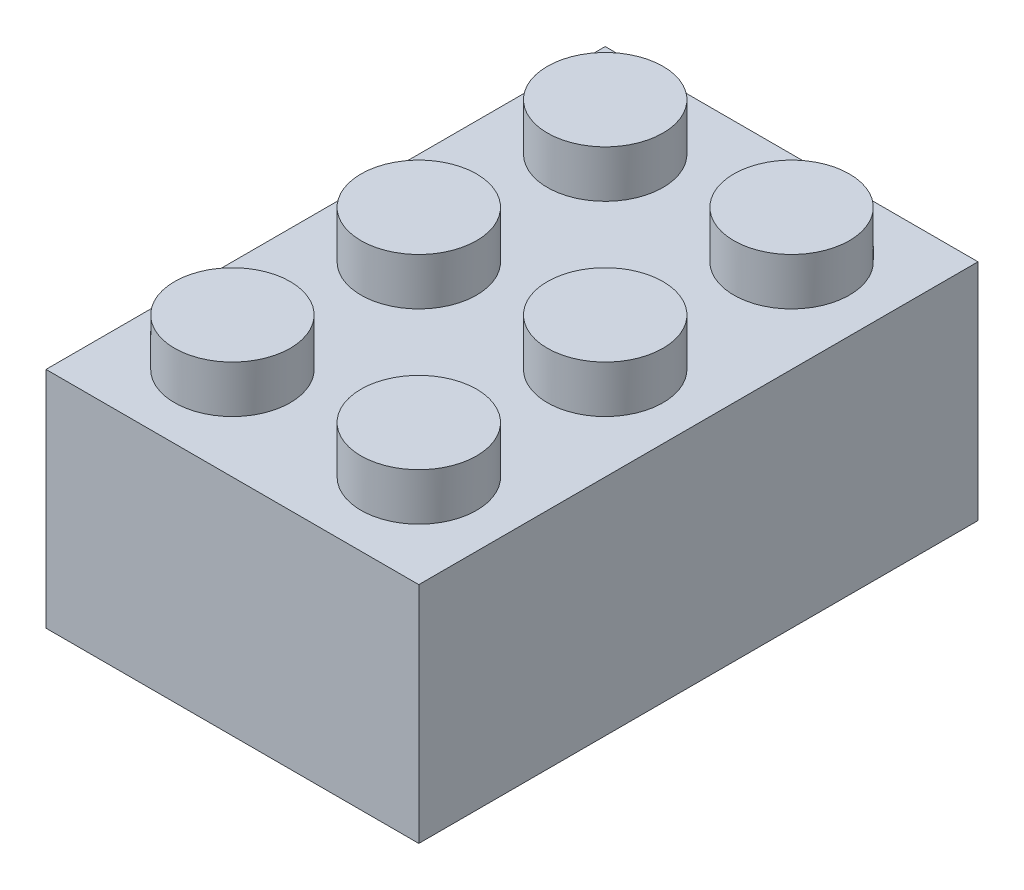
SolidWorks part; units mm, degrees
ref_plane "Front Plane" through (0, 0, 0) normal (0, 0, 1) x (1, 0, 0)
ref_plane "Top Plane" through (0, 0, 0) normal (0, 1, 0) x (1, 0, 0)
ref_plane "Right Plane" through (0, 0, 0) normal (1, 0, 0) x (0, 0, -1)
sketch "stencil" plane through (0, 0, 0) normal (0, 1, 0) x (1, 0, 0)
  line L2 (14.3, 22.2) -> (1.5, 22.2)
  line L29 (15.8, 23.7) -> (0, 23.7)
  line L37 (15.8, 23.7) -> (15.8, 0)
  line L38 (15.8, 0) -> (0, 0)
  line L39 (0, 23.7) -> (0, 0)
  line L40 (7.9, 0) -> (7.9, 23.7) construction
  line L41 (15.8, 11.85) -> (0, 11.85) construction
  line L50 (1.5, 22.2) -> (1.5, 1.5)
  line L51 (14.3, 1.5) -> (1.5, 1.5)
  line L52 (14.3, 22.2) -> (14.3, 1.5)
  circle A43 centre (3.95, 3.95) radius 2.45
  circle A44 centre (7.9, 7.9) radius 3.25
  circle A46 centre (3.95, 11.85) radius 2.45
  circle A47 centre (7.9, 15.8) radius 3.25
  circle A49 centre (3.95, 19.75) radius 2.45
  circle A50 centre (11.85, 19.75) radius 2.45
  circle A51 centre (11.85, 11.85) radius 2.45
  circle A52 centre (11.85, 3.95) radius 2.45
  circle A53 centre (7.9, 15.8) radius 2.45
  circle A54 centre (7.9, 7.9) radius 2.45
  point P1 (0, 0)
  point P6 (3.95, -15.8)
  point P9 (7.9, -15.8)
  point P10 (7.9, -11.85)
  point P13 (3.95, -7.9)
  point P15 (7.9, -7.9)
  point P17 (7.9, -3.95)
  point P18 (3.95, 0)
  point P21 (7.9, 0)
  point P25 (7.9, 3.95)
  point P27 (3.95, 7.9)
  point P28 (7.9, 7.9)
  point P29 (0, -11.85)
  point P30 (0, -7.9)
  point P31 (0, 3.95)
  point P34 (0, -3.95)
  point P35 (3.95, 0)
  point P36 (0, 15.8)
  point P37 (0, 23.7)
  point P38 (7.9, 23.7)
  point P39 (15.8, 23.7)
  point P40 (15.8, 15.8)
  point P41 (15.8, 7.9)
  point P48 (15.8, 0)
  point P49 (7.9, 0)
  point P51 (11.85, 0)
  point P52 (3.95, 3.95)
  point P53 (7.9, 3.95)
  point P55 (11.85, 3.95)
  point P56 (3.95, 7.9)
  point P57 (7.9, 7.9)
  point P58 (11.85, 7.9)
  point P59 (3.95, 11.85)
  point P60 (7.9, 11.85)
  point P61 (11.85, 11.85)
  point P64 (3.95, 15.8)
  point P65 (7.9, 15.8)
  point P66 (11.85, 15.8)
  point P68 (3.95, 19.75)
  point P69 (7.9, 19.75)
  point P70 (11.85, 19.75)
  point P71 (0, 3.95)
  point P73 (0, 7.9)
  point P75 (0, 11.85)
  point P77 (0, 15.8)
  point P79 (0, 19.75)
  point P81 (15.8, 3.95)
  point P83 (15.8, 7.9)
  point P85 (15.8, 11.85)
  point P87 (15.8, 15.8)
  point P88 (15.8, 19.75)
  point P91 (0, 23.7)
  point P93 (3.95, 23.7)
  point P94 (7.9, 23.7)
  point P95 (11.85, 23.7)
  point P96 (15.8, 23.7)
  point P97 (7.9, 11.85)
  point P118 (7.9, 11.85)
  dimension "D5" = 4.9
  dimension "D7" = 6.5
  dimension "D3" = 3.95
  dimension "D4" = 3.95
  dimension "D9" = 23.7
  dimension "D10" = 15.8
  dimension "D6" = 0.8
  dimension "D8" = 0.8
  dimension "D11" = 1.5
  dimension "D1" = 5
  dimension "D2" = 7
sketch "Sketch1" plane through (0, 0, 0) normal (0, 1, 0) x (1, 0, 0)
  line L9 (15.8, 23.7) -> (0, 23.7)
  line L10 (15.8, 23.7) -> (15.8, 0)
  line L11 (15.8, 0) -> (0, 0)
  line L12 (0, 23.7) -> (0, 0)
  line L13 (7.9, 0) -> (7.9, 23.7) construction
  line L14 (15.8, 11.85) -> (0, 11.85) construction
  point P0 (7.9, 11.85)
extrude "Boss-Extrude1" add sketch "Sketch1" along normal mid plane 9.5
sketch "Sketch2" plane through (0, 4.75, 0) normal (0, 1, 0) x (1, 0, 0)
  circle A14 centre (3.95, 3.95) radius 2.45
  circle A15 centre (11.85, 3.95) radius 2.45
  circle A16 centre (11.85, 11.85) radius 2.45
  circle A17 centre (3.95, 11.85) radius 2.45
  circle A18 centre (3.95, 19.75) radius 2.45
  circle A19 centre (11.85, 19.75) radius 2.45
  circle A20 centre (3.95, 3.95) radius 2.45 construction
extrude "Boss-Extrude2" add sketch "Sketch2" along normal blind 2
sketch "Sketch4" plane through (0, -4.75, 0) normal (0, -1, 0) x (1, 0, 0)
  line L5 (14.3, -22.2) -> (1.5, -22.2)
  line L7 (14.3, -22.2) -> (14.3, -1.5)
  line L11 (14.3, -1.5) -> (1.5, -1.5)
  line L12 (1.5, -22.2) -> (1.5, -1.5)
  line L13 (7.9, -1.5) -> (7.9, -22.2) construction
  line L14 (14.3, -11.85) -> (1.5, -11.85) construction
  point P0 (7.9, -11.85)
extrude "Cut-Extrude1" cut sketch "Sketch4" against normal blind 4
sketch "Sketch5" plane through (0, -0.75, 0) normal (0, -1, 0) x (1, 0, 0)
  circle A1 centre (7.9, -7.9) radius 2.45
  circle A5 centre (7.9, -15.8) radius 2.45
  circle A12 centre (7.9, -15.8) radius 3.25
  circle A13 centre (7.9, -7.9) radius 3.25
  circle A14 centre (7.9, -15.8) radius 2.45 construction
  circle A15 centre (7.9, -7.9) radius 3.25 construction
extrude "Boss-Extrude3" add sketch "Sketch5" along normal up to surface (4 mm away) up to face at (7.9, -4.75, -11.85)
equation "\"t\"= 0.0'tolerance"
equation "\"D9@stencil\"=23.70-\"t\""
equation "\"D10@stencil\"=15.80-\"t\""
equation "\"D11@stencil\"=1.50-\"t\""
equation "\"D7@stencil\"=6.50-\"t\""
